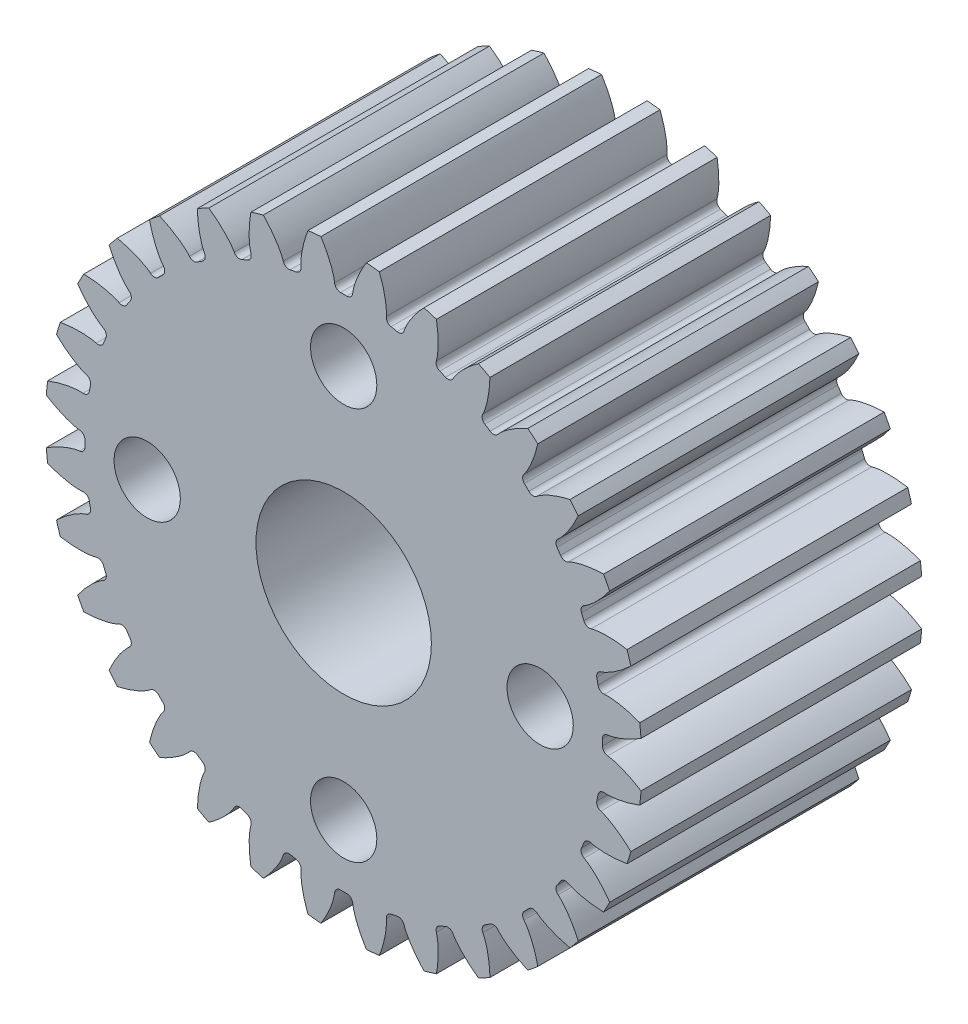
SolidWorks part; units mm, degrees
material "Plain Carbon Steel"
ref_plane "Front Plane" through (0, 0, 0) normal (0, 0, 1) x (1, 0, 0)
ref_plane "Top Plane" through (0, 0, 0) normal (0, 1, 0) x (1, 0, 0)
ref_plane "Right Plane" through (0, 0, 0) normal (1, 0, 0) x (0, 0, -1)
sketch "Sketch1" plane through (0, 0, 0) normal (0, 0, 1) x (1, 0, 0)
  line L0 (0, 0) -> (0, 12.7) construction
  line L1 (-4.0817, 14.1856) -> (4.0817, 11.2144) construction
  circle A0 centre (0, 0) radius 11.7078 construction
  circle A1 centre (0, 0) radius 13.4938 construction
  circle A2 centre (0, 0) radius 12.7 construction
  circle A3 centre (0, 0) radius 11.9341 construction
  point P8 (406.4, 0)
  point P13 (406.4, 0)
  dimension "OD | Outside Diameter" = 26.9875
  dimension "Root Diameter" = 23.4156
  dimension "Gear Pitch Diameter" = 25.4
  dimension "Base Diameter" = 23.8682
  dimension "Pressure Angle" = 20
  dimension "Number of Teeth" = 812.8
  dimension "Gear Pitch | Diametral Pitch" = 812.8
sketch "Sketch2" plane through (0, 0, 0) normal (1, 0, 0) x (0, 0, -1)
  line L0 (-6.35, 0) -> (6.35, 0) construction
  point P2 (7.1437, 0)
  point P5 (13.8906, 0)
  point P6 (-7.1437, 0)
  dimension "Length" = 12.7
  dimension "D1" = 13.4937
  dimension "D2" = 20.2406
  dimension "D3" = 13.4937
sketch "Sketch3" plane through (0, 0, 0) normal (0, 0, 1) x (1, 0, 0)
  circle A0 centre (0, 0) radius 13.4938
  circle A1 centre (0, 0) radius 13.4937 construction
extrude "Boss-Extrude1" add sketch "Sketch3" against normal up to vertex (6.35 mm away) and the other way up to vertex (6.35 mm away) up to point (0, 0, -6.35) other way up to point (0, 0, 6.35)
sketch "Sketch4" plane through (0, 0, 0) normal (0, 0, 1) x (1, 0, 0)
  line L0 (0, 0) -> (11.701, 0.4001) construction
  line L2 (0, 0) -> (11.701, -0.4001) construction
  line L4 (11.701, 0.4001) -> (11.9271, 0.4079)
  line L5 (11.9271, -0.4079) -> (11.701, -0.4001)
  arc A0 (11.701, 0.4001) -> (11.701, -0.4001) centre (0, 0) cw
  arc A3 (13.4545, 1.0288) -> (13.4545, -1.0288) centre (0, 0) cw
  circle A4 centre (0, 0) radius 13.4937 construction
  spline S0 degree 4 poles (11.9271, 0.4079) (11.9296, 0.408) (11.9365, 0.4084) (11.9495, 0.4095) (11.9706, 0.4117) (11.9976, 0.4153) (12.0324, 0.4207) (12.0733, 0.4281) (12.1181, 0.4373) (12.1668, 0.4485) (12.2153, 0.4607) (12.2636, 0.4738) (12.3116, 0.4878) (12.3697, 0.5057) (12.4391, 0.5286) (12.52, 0.5574) (12.6114, 0.5926) (12.7042, 0.631) (12.7953, 0.6709) (12.8869, 0.7137) (12.9752, 0.7568) (13.0666, 0.8041) (13.1507, 0.8491) (13.2444, 0.9022) (13.3199, 0.9459) (13.419, 1.0064) (13.4774, 1.0431) (13.5454, 1.087) (13.5756, 1.107) (13.5941, 1.1193) knots 0 0 0 0 0 0.005377 0.015084 0.028532 0.04661 0.064855 0.092111 0.119476 0.146842 0.174209 0.201575 0.228941 0.256307 0.307035 0.361767 0.4165 0.471232 0.525964 0.580697 0.635429 0.690161 0.744894 0.799626 0.854358 0.909091 0.954545 1 1 1 1 1 construction
  spline S1 degree 4 poles (11.9271, 0.4079) (11.9296, 0.408) (11.9365, 0.4084) (11.9495, 0.4095) (11.9706, 0.4117) (11.9976, 0.4153) (12.0324, 0.4207) (12.0733, 0.4281) (12.1181, 0.4373) (12.1668, 0.4485) (12.2153, 0.4607) (12.2636, 0.4738) (12.3116, 0.4878) (12.3697, 0.5057) (12.4391, 0.5286) (12.52, 0.5574) (12.6114, 0.5926) (12.7042, 0.631) (12.7953, 0.6709) (12.8869, 0.7137) (12.9752, 0.7568) (13.0666, 0.8041) (13.1507, 0.8491) (13.2444, 0.9022) (13.3199, 0.9459) (13.3975, 0.9933) (13.4352, 1.0167) (13.4545, 1.0288) knots 0 0 0 0 0 0.005377 0.015084 0.028532 0.04661 0.064855 0.092111 0.119476 0.146842 0.174209 0.201575 0.228941 0.256307 0.307035 0.361767 0.4165 0.471232 0.525964 0.580697 0.635429 0.690161 0.744894 0.799626 0.854358 0.909091 0.909091 0.909091 0.909091 0.909091
  spline S2 degree 4 poles (11.9271, -0.4079) (11.9296, -0.408) (11.9365, -0.4084) (11.9495, -0.4095) (11.9706, -0.4117) (11.9976, -0.4153) (12.0324, -0.4207) (12.0733, -0.4281) (12.1181, -0.4373) (12.1668, -0.4485) (12.2153, -0.4607) (12.2636, -0.4738) (12.3116, -0.4878) (12.3697, -0.5057) (12.4391, -0.5286) (12.52, -0.5574) (12.6114, -0.5926) (12.7042, -0.631) (12.7953, -0.6709) (12.8869, -0.7137) (12.9752, -0.7568) (13.0666, -0.8041) (13.1507, -0.8491) (13.2444, -0.9022) (13.3199, -0.9459) (13.419, -1.0064) (13.4774, -1.0431) (13.5454, -1.087) (13.5756, -1.107) (13.5941, -1.1193) knots 0 0 0 0 0 0.005377 0.015084 0.028532 0.04661 0.064855 0.092111 0.119476 0.146842 0.174209 0.201575 0.228941 0.256307 0.307035 0.361767 0.4165 0.471232 0.525964 0.580697 0.635429 0.690161 0.744894 0.799626 0.854358 0.909091 0.954545 1 1 1 1 1 construction
  spline S3 degree 4 poles (11.9271, -0.4079) (11.9296, -0.408) (11.9365, -0.4084) (11.9495, -0.4095) (11.9706, -0.4117) (11.9976, -0.4153) (12.0324, -0.4207) (12.0733, -0.4281) (12.1181, -0.4373) (12.1668, -0.4485) (12.2153, -0.4607) (12.2636, -0.4738) (12.3116, -0.4878) (12.3697, -0.5057) (12.4391, -0.5286) (12.52, -0.5574) (12.6114, -0.5926) (12.7042, -0.631) (12.7953, -0.6709) (12.8869, -0.7137) (12.9752, -0.7568) (13.0666, -0.8041) (13.1507, -0.8491) (13.2444, -0.9022) (13.3199, -0.9459) (13.3975, -0.9933) (13.4352, -1.0167) (13.4545, -1.0288) knots 0 0 0 0 0 0.005377 0.015084 0.028532 0.04661 0.064855 0.092111 0.119476 0.146842 0.174209 0.201575 0.228941 0.256307 0.307035 0.361767 0.4165 0.471232 0.525964 0.580697 0.635429 0.690161 0.744894 0.799626 0.854358 0.909091 0.909091 0.909091 0.909091 0.909091
  dimension "D1" = 23.4156
extrude "Cut-Extrude1" cut sketch "Sketch4" against normal through all both and the other way through all
fillet "Fillet1" radius 0.2663 2 edges at (11.701, -0.4001, 0) (11.701, 0.4001, 0)
pattern_circular "CirPattern1" count 32 over 360 about axis through (0, 0, 6.35) along (0, 0, -1) of "Cut-Extrude1", "Fillet1"
sketch "Sketch5" plane through (0, 0, 6.35) normal (0, 0, 1) x (1, 0, 0)
  point P0 (0, 0)
hole_wizard "5/16 (0.3125) Dowel Hole1" positions "Sketch5" profile "Sketch6" hole size "5/16" standard "ANSI Inch" end condition through all
sketch "Sketch6" plane through (0, 0, 6.35) normal (1, 0, 0) x (0, -1, 0)
  line L0 (0, 0) -> (0, 12.7)
  line L1 (0, 12.7) -> (3.9687, 12.7)
  line L2 (3.9687, 12.7) -> (3.9687, 0)
  line L5 (3.9687, 0) -> (0, 0)
  line L11 (0, -6.35) -> (0, 107.95) construction
  dimension "Thru Hole Dia." = 7.9375
  dimension "Thru Hole Depth" = 12.7
sketch "Sketch7" plane through (0, 0, 6.35) normal (0, 0, 1) x (1, 0, 0)
  point P0 (0, 0)
  point P1 (0, 8.89)
  dimension "D1" = 8.89
ref_axis "Axis1" through (0, 0, -6.35) along (0, 0, 1)
hole_wizard "Ø3.0mm Dowel Hole1" positions "Sketch7" profile "Sketch8" hole size "Ø3.0" standard "ANSI Metric" end condition through all
sketch "Sketch8" plane through (0, 0, 6.35) normal (1, 0, 0) x (0, -1, 0)
  line L0 (0, 0) -> (0, 12.7)
  line L1 (0, 12.7) -> (1.5, 12.7)
  line L2 (1.5, 12.7) -> (1.5, 0)
  line L5 (1.5, 0) -> (0, 0)
  line L11 (0, -6.35) -> (0, 107.95) construction
  dimension "Thru Hole Dia." = 3
  dimension "Thru Hole Depth" = 12.7
pattern_circular "CirPattern2" count 4 over 360 about axis through (0, 0, 6.35) along (0, 0, 1) of "Ø3.0mm Dowel Hole1"
equation "\"Root Diameter@Sketch1\"=\"Root Diameter\""
equation "\"OD | Outside Diameter@Sketch1\"=\"Outside Diameter\""
equation "\"D1@CirPattern1\"=\"Number of Teeth\""
equation "\"Diametral Pitch\"=32"
equation "\"Number of Teeth\"= 32"
equation "\"Pressure Angle\"=20"
equation "\"Pitch Diameter\"= \"Number of Teeth\" / \"Diametral Pitch\""
equation "\"Base Diameter\"= \"Pitch Diameter\" * cos ( \"Pressure Angle\" )"
equation "\"Outside Diameter\"= ( \"Number of Teeth\" + 2 ) / \"Diametral Pitch\""
equation "\"Dedendum\"= 1.25 / \"Diametral Pitch\""
equation "\"Root Diameter\"= \"Pitch Diameter\" - ( 2 * \"Dedendum\" )"
equation "\"Pitch Angle\"= 360deg / \"Number of Teeth\""
equation "\"Alpha\"= sqr ( \"Pitch Diameter\" ^ 2 - \"Base Diameter\" ^ 2 ) / \"Base Diameter\" * 180 / PI - \"Pressure Angle\""
equation "\"Beta\"= ( \"Pitch Angle\" / 4 - \"Alpha\" )"
equation "\"Phi\"= sqr ( ( \"Outside Diameter\" / 2 ) ^ 2 - ( \"Base Diameter\" / 2 ) ^ 2 ) / ( \"Base Diameter\" / 2 )"
equation "\"Addendum\"= 1 / \"Diametral Pitch\""
equation "\"WorkingDepth\"= 2 / \"Diametral Pitch\""
equation "\"WholeDepth\"= 2.25 / \"Diametral Pitch\""
equation "\"Clearance\"= 0.25 / \"Diametral Pitch\""
equation "\"ToothThickness\"= ( pi * 2 ) / \"Diametral Pitch\""
equation "\"CircularPitch\"= pi / \"Diametral Pitch\""
equation "\"Number of Teeth@Sketch1\"=\"Number of Teeth\""
equation "\"Gear Pitch | Diametral Pitch@Sketch1\"=\"Diametral Pitch\""
equation "\"Pressure Angle@Sketch1\"=\"Pressure Angle\""
equation "\"Gear Pitch Diameter@Sketch1\"=\"Pitch Diameter\""
equation "\"Base Diameter@Sketch1\"=\"Base Diameter\""
equation "\"Fillet\"= \"Clearance\" * cos ( \"Pressure Angle\" ) * tan ( ( 90 + \"Pressure Angle\" ) / 2 )"
equation "\"D1@Fillet1\"=\"Fillet\""
equation "\"D1@Sketch4\"=if( \"Base Diameter\">\"Root Diameter\",\"Root Diameter\",\"Base Diameter\"-.00001)"
equation "\"D1@Sketch2\"=\"OD | Outside Diameter@Sketch1\"*2*0.5*0.5"
equation "\"D2@Sketch2\"=\"D1@Sketch2\"*1.5"
equation "\"D3@Sketch2\"=\"D1@Sketch2\""
equation "\"Length\"= .5in"
equation "\"Length@Sketch2\"= \"Length\""
